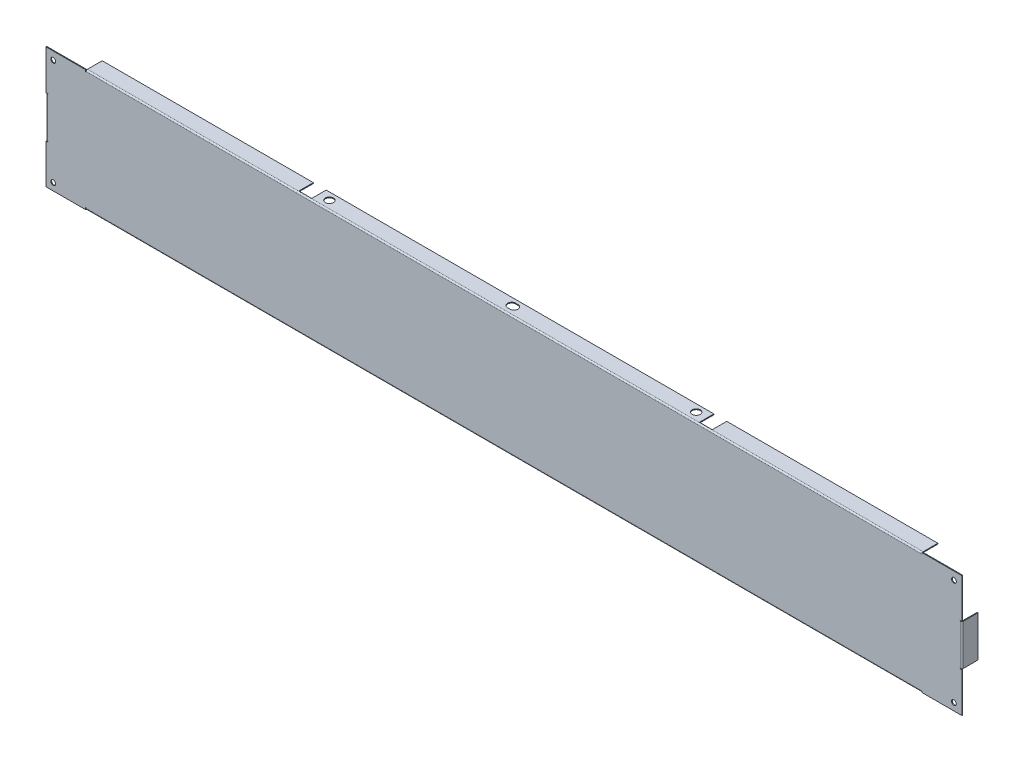
SolidWorks part; units mm, degrees
note: The reader was unsure of these and kept them because the rebuilt part matched: flange length of "边线-法兰1", "边线-法兰2", "边线-法兰4".
ref_plane "前视基准面" through (0, 0, 0) normal (0, 0, 1) x (1, 0, 0)
ref_plane "上视基准面" through (0, 0, 0) normal (0, 1, 0) x (1, 0, 0)
ref_plane "右视基准面" through (0, 0, 0) normal (1, 0, 0) x (0, 0, -1)
sketch "草图1" plane through (0, 0, 0) normal (0, 0, 1) x (1, 0, 0)
  line L1 (-570.5, 75.5) -> (570.5, 75.5)
  line L2 (-570.5, 75.5) -> (-570.5, -75.5)
  line L3 (-570.5, -75.5) -> (570.5, -75.5)
  line L4 (570.5, 75.5) -> (570.5, -75.5)
  line L5 (-570.5, 75.5) -> (570.5, -75.5) construction
  line L6 (-570.5, -75.5) -> (570.5, 75.5) construction
  point P0 (0, 0)
  dimension "D1" = 1141
  dimension "D2" = 151
sheet metal parameters "钣金1" thickness 1 parameters "D1"=0.7366
base flange "基体-法兰1" sketch "草图1" thickness 1 reverse thickness direction no parameters "D1"=0.7366
edge flange "边线-法兰1" sketch "草图5" flange angle 90 flange length 20 flange position material inside bend radius 0.7366 thickness 1 relief rectangular parameters "D6"=10
sketch "草图5" plane through (570.5, 0, -1) normal (1, 0, 0) x (0, -1, 0)
  line L2 (-25.5, 0) -> (-25.5, 19)
  line L3 (-25.5, 19) -> (25.5, 19)
  line L4 (25.5, 19) -> (25.5, 0)
  line L7 (75.5, 0) -> (-75.5, 0) construction
  line L8 (25.5, 0) -> (-25.5, 0)
  line L9 (-75.5, 0) -> (-75.5, -1) construction
  line L10 (75.5, 0) -> (75.5, -1) construction
  line L11 (75.5, -1) -> (-75.5, -1) construction
  dimension "D1" = 50
  dimension "D2" = 50
  dimension "D3" = 20
bend "边线折弯1" bend radius 0.7366 bend angle 90 parameters "D5"=1
edge flange "边线-法兰2" sketch "草图8" flange angle 90 flange length 20 flange position material inside bend radius 0.7366 thickness 1 relief rectangular parameters "D6"=10
sketch "草图8" plane through (0, 75.5, -1) normal (0, 1, 0) x (1, 0, 0)
  line L0 (570.5, 0) -> (-570.5, 0) construction
  line L1 (520.5, 0) -> (-520.5, 0)
  line L2 (-520.5, 0) -> (-520.5, 19)
  line L3 (-520.5, 19) -> (-257.5, 19)
  line L4 (520.5, 19) -> (520.5, 0)
  line L5 (570.5, -1) -> (-570.5, -1) construction
  line L6 (570.5, 0) -> (570.5, -1) construction
  line L7 (-570.5, 0) -> (-570.5, -1) construction
  line L8 (-241.5, 19) -> (241.5, 19)
  line L9 (257.5, 19) -> (520.5, 19)
  line L10 (-257.5, 19) -> (-257.5, 1)
  line L11 (-257.5, 1) -> (-241.5, 1)
  line L12 (-241.5, 19) -> (-241.5, 1)
  line L14 (241.5, 19) -> (241.5, 1)
  line L15 (241.5, 1) -> (257.5, 1)
  line L16 (257.5, 19) -> (257.5, 1)
  dimension "D1" = 20
  dimension "D2" = 50
  dimension "D3" = 50
  dimension "D4" = 263
  dimension "D5" = 16
  dimension "D6" = 483
  dimension "D7" = 16
  dimension "D8" = 2
bend "边线折弯2" bend radius 0.7366 bend angle 90 parameters "D5"=2
edge flange "边线-法兰4" sketch "草图14" flange angle 90 flange length 20 flange position material inside bend radius 0.7366 thickness 1 relief rectangular parameters "D6"=10
sketch "草图14" plane through (-570.5, 0, -1) normal (-1, 0, 0) x (0, 1, 0)
  line L2 (-25.5, 0) -> (-25.5, 19)
  line L3 (-25.5, 19) -> (25.5, 19)
  line L4 (25.5, 19) -> (25.5, 0)
  line L5 (75.5, 0) -> (-75.5, 0) construction
  line L6 (25.5, 0) -> (-25.5, 0)
  line L7 (-75.5, 0) -> (-75.5, -1) construction
  line L8 (75.5, 0) -> (75.5, -1) construction
  line L9 (75.5, -1) -> (-75.5, -1) construction
  dimension "D1" = 50
  dimension "D2" = 50
  dimension "D3" = 20
bend "边线折弯4" bend radius 0.7366 bend angle 90 parameters "D5"=4
mirror "镜向1" about plane through (0, 0, 0) normal (0, 1, 0) of "边线-法兰2"
bend "镜向折弯1" bend radius 0.7366 bend angle 90 parameters "D5"=5
sketch "草图15" plane through (0, 75.5, 0) normal (0, 1, 0) x (1, 0, 0)
  line L0 (-1.5, 11) -> (1.5, 11) construction
  line L1 (-1.5, 16) -> (1.5, 16)
  line L2 (-570.5, 1) -> (-570.5, 0) construction
  line L3 (570.5, 1) -> (570.5, 0) construction
  line L4 (241.5, 20) -> (-241.5, 20) construction
  line L5 (-1.5, 6) -> (1.5, 6)
  circle A0 centre (-228.5, 11) radius 5
  circle A1 centre (228.5, 11) radius 5
  arc A2 (-1.5, 16) -> (-1.5, 6) centre (-1.5, 11) ccw
  arc A3 (1.5, 6) -> (1.5, 16) centre (1.5, 11) ccw
  point P12 (0, 11)
  dimension "D1" = 10
  dimension "D3" = 342
  dimension "D2" = 342
  dimension "D4" = 9
  dimension "D5" = 3
  dimension "D6" = 10
  dimension "D7" = 228.5
extrude "切除-拉伸1" cut sketch "草图15" against normal through all normal cut yes
sketch "草图16" plane through (0, 0, -1) normal (0, 0, -1) x (-1, 0, 0)
  circle A0 centre (-560.5, -66.5) radius 3
  circle A1 centre (-560.5, 65.5) radius 3
  circle A2 centre (561.5, -66.5) radius 3
  circle A3 centre (561.5, 65.5) radius 3
  dimension "D1" = 6
extrude "切除-拉伸2" cut sketch "草图16" against normal through all normal cut yes
flat pattern "平板型式1" [suppressed]
sketch "折弯-线1" plane through (0, 0, 0) normal (0, 1, 0) x (-1, 0, 0)
bend of the flat pattern "展开-<边线折弯1>1"
bend of the flat pattern "展开-<边线折弯2>1"
bend of the flat pattern "展开-<边线折弯4>1"
bend of the flat pattern "展开-<镜向折弯1>1"
